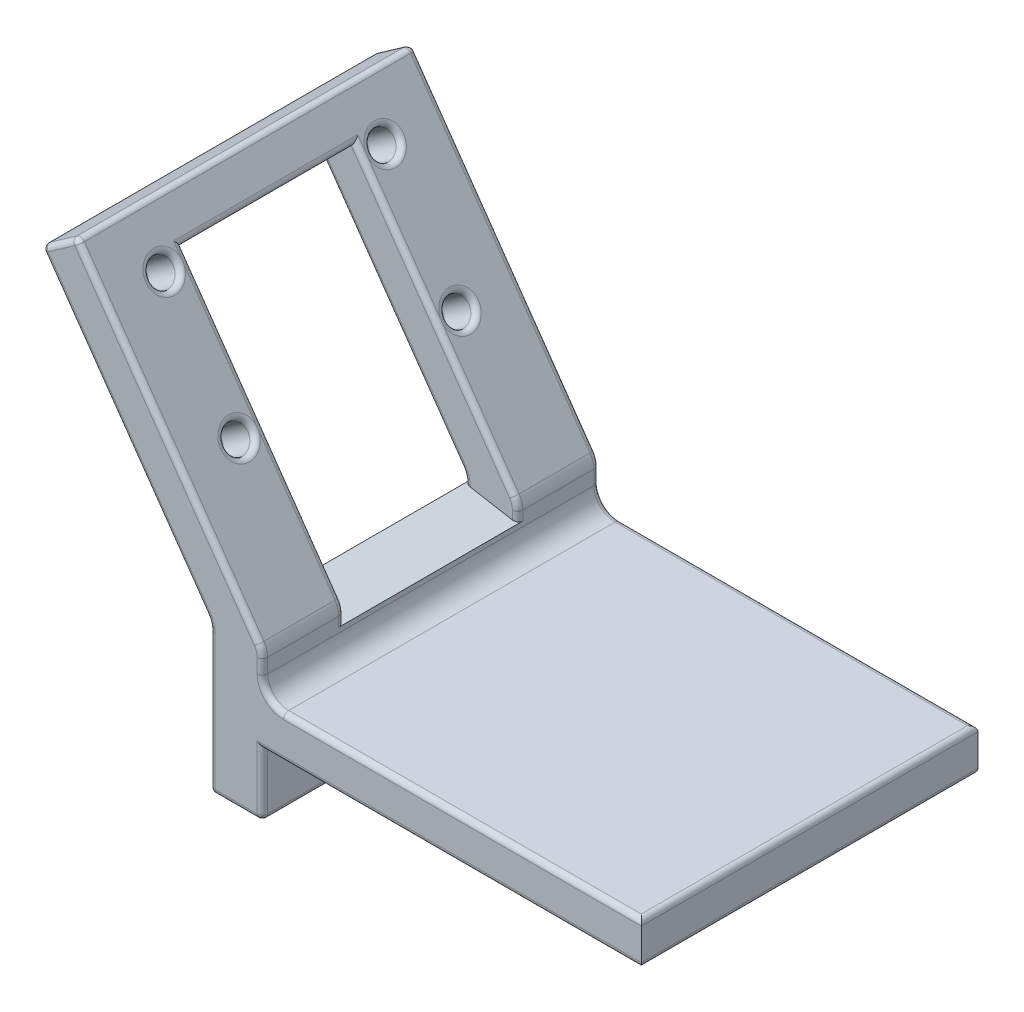
SolidWorks part; units mm, degrees
ref_plane "Plan de face" through (0, 0, 0) normal (0, 0, 1) x (1, 0, 0)
ref_plane "Plan de dessus" through (0, 0, 0) normal (0, 1, 0) x (1, 0, 0)
ref_plane "Plan de droite" through (0, 0, 0) normal (1, 0, 0) x (0, 0, -1)
sketch "Esquisse1" plane through (0, 0, 0) normal (0, 0, 1) x (1, 0, 0)
  line L0 (0, 0) -> (0, -6)
  line L1 (0, 0) -> (36, 0)
  line L2 (0, 0) -> (0, 4) construction
  line L3 (0, 4) -> (36, 4)
  line L4 (36, 0) -> (36, 4)
  line L5 (0, -6) -> (-5, -6)
  line L6 (-5, -6) -> (-5, 8)
  line L7 (-5, 8) -> (-21.0601, 30.9363)
  line L8 (-21.0601, 30.9363) -> (-17.7051, 33.2855)
  line L9 (-17.7051, 33.2855) -> (0, 8)
  line L10 (0, 8) -> (0, 4)
  line L11 (-5, 8) -> (0, 8) construction
  dimension "D1" = 36
  dimension "D2" = 5
  dimension "D3" = 4
  dimension "D4" = 4
  dimension "D5" = 6
  dimension "D6" = 28
  dimension "D7" = 145
extrude "Boss.-Extru.1" add sketch "Esquisse1" along normal blind 32
sketch "Esquisse2" plane through (-5, 0, 0) normal (-1, 0, 0) x (0, 0, 1)
  line L0 (8, -2.7) -> (24, -2.7) construction
  line L1 (32, -6) -> (0, -6) construction
  line L2 (8, -2.7) -> (0, -2.7) construction
  line L3 (0, 8) -> (0, -6) construction
  line L4 (24, -2.7) -> (32, -2.7) construction
  line L5 (32, 8) -> (32, -6) construction
  circle A0 centre (8, -2.7) radius 1.25
  circle A1 centre (24, -2.7) radius 1.25
  dimension "D2" = 2.5
  dimension "D1" = 16
  dimension "D3" = 3.3
extrude "Enlèv. mat.-Extru.1" cut sketch "Esquisse2" against normal through all
sketch "Esquisse3" plane through (0.4037, 0.2827, 0) normal (-0.8192, -0.5736, 0) x (0, 0, 1)
  line L0 (32, 9.4211) -> (0, 9.4211) construction
  line L1 (7.75, 9.4211) -> (24.25, 9.4211)
  line L2 (7.75, 9.4211) -> (7.75, 33.4211)
  line L3 (7.75, 33.4211) -> (24.25, 33.4211)
  line L4 (24.25, 9.4211) -> (24.25, 33.4211)
  line L5 (7.75, 9.4211) -> (0, 9.4211) construction
  line L6 (24.25, 9.4211) -> (32, 9.4211) construction
  line L7 (32, 37.4211) -> (0, 37.4211) construction
  line L8 (5.5, 32.4211) -> (0, 32.4211) construction
  line L9 (0, 37.4211) -> (0, 9.4211) construction
  line L10 (5.5, 32.4211) -> (26.5, 32.4211) construction
  line L11 (26.5, 32.4211) -> (32, 32.4211) construction
  line L12 (32, 37.4211) -> (32, 9.4211) construction
  line L13 (5.5, 32.4211) -> (5.5, 20.0211) construction
  line L14 (26.5, 32.4211) -> (26.5, 20.0211) construction
  circle A0 centre (5.5, 32.4211) radius 1.25
  circle A1 centre (5.5, 20.0211) radius 1.25
  circle A2 centre (26.5, 32.4211) radius 1.25
  circle A3 centre (26.5, 20.0211) radius 1.25
  dimension "D4" = 2.5
  dimension "D1" = 16.5
  dimension "D2" = 4
  dimension "D3" = 1
  dimension "D5" = 21
  dimension "D6" = 12.4
extrude "Enlèv. mat.-Extru.2" cut sketch "Esquisse3" against normal through all
sketch "Esquisse4" plane through (-5, 0, 0) normal (-1, 0, 0) x (0, 0, 1)
  circle A0 centre (8, -2.7) radius 2.15
  circle A1 centre (24, -2.7) radius 2.15
  dimension "D1" = 4.3
extrude "Enlèv. mat.-Extru.3" cut sketch "Esquisse4" against normal blind 2
chamfer "Chanfrein1" distance 5 angle 45 1 edges at (-1.6449, 10.3492, 16)
fillet "Congé1" radius 2 5 edges at (-5, 8, 28.125) (-5, 8, 3.875) (0, 8, 3.875) (0, 8, 28.125) (0, 4, 16)
fillet "Congé2" radius 0.5 58 edges at (-5, 7.3601, 7.75) (-5.0926, 7.9708, 7.75) (-5, 0.6847, 0) (-5.0926, 7.9708, 0) (-5, 0.6847, 32) (-5.0926, 7.9708, 32) (-5, 7.3601, 24.25) (-5.0926, 7.9708, 24.25) (0, 6.9193, 24.25) (-0.0926, 7.9708, 24.25) (0, 6.9193, 7.75) (-0.0926, 7.9708, 7.75) (-0.0926, 7.9708, 32) (0, 6.6847, 32) (0.5858, 4.5858, 32) (-0.0926, 7.9708, 0) (0, 6.6847, 0) (0.5858, 4.5858, 0) (0, -3.95, 8) (0, -3.95, 24) (-5, -6, 16) (-2.5, -6, 32) (0, -6, 16) (-2.5, -6, 0) (-18.7658, 27.6596, 16) (-12.0638, 18.0881, 7.75) (-13.2109, 19.7264, 0) (-13.2109, 19.7264, 32) (-12.0638, 18.0881, 24.25) (-10.3629, 15.6591, 5.5) (-17.4753, 25.8166, 5.5) (-10.3629, 15.6591, 26.5) (-17.4753, 25.8166, 26.5) (-15.4108, 30.0089, 16) (-7.8862, 19.2627, 24.25) (-9.0334, 20.901, 32) (-9.0334, 20.901, 0) (-7.8862, 19.2627, 7.75) (-7.0079, 18.0083, 5.5) (-14.1202, 28.1658, 5.5) (-7.0079, 18.0083, 26.5) (-14.1202, 28.1658, 26.5) (-17.7051, 33.2855, 16) (-19.3826, 32.1109, 32) (-21.0601, 30.9363, 16) (-19.3826, 32.1109, 0) (36, 4, 16) (19, 4, 32) (19, 4, 0) (0, -3, 0) (0, -3, 32) (18, 0, 0) (36, 0, 16) (18, 0, 32) (-3, -3.95, 8) (-3, -3.95, 24) (-5, -4.85, 24) (-5, -4.85, 8)
